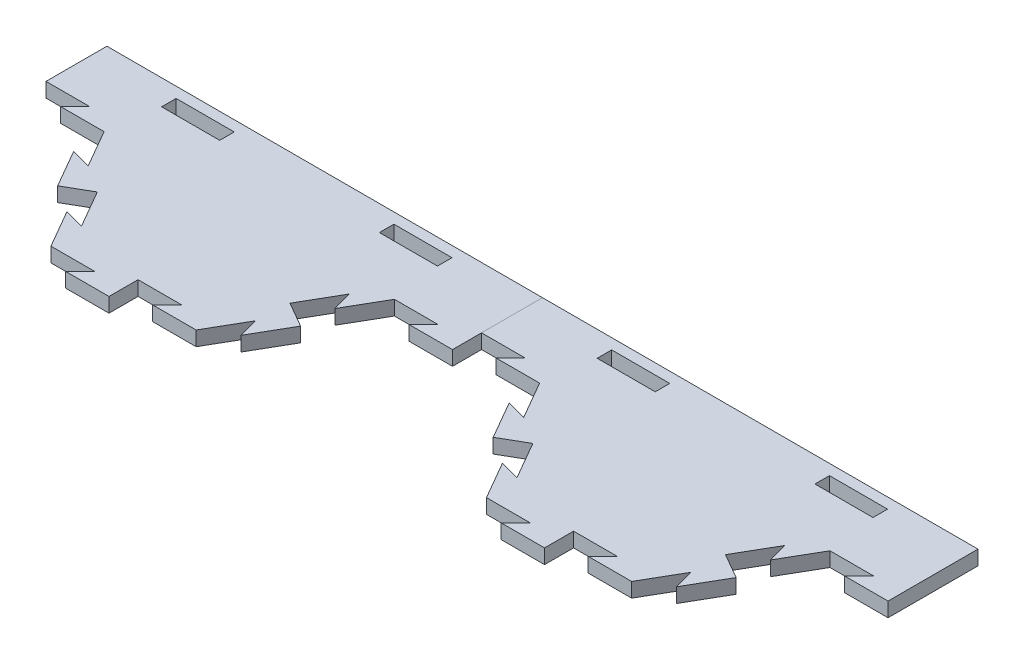
SolidWorks part; units mm, degrees
material "Cedar"
ref_plane "Front Plane" through (0, 0, 0) normal (0, 0, 1) x (1, 0, 0)
ref_plane "Top Plane" through (0, 0, 0) normal (0, 1, 0) x (1, 0, 0)
ref_plane "Right Plane" through (0, 0, 0) normal (1, 0, 0) x (0, 0, -1)
sketch "Sketch1" plane through (0, 0, 0) normal (0, 1, 0) x (1, 0, 0)
  line L0 (0, 0) -> (63.5, 0) construction
  line L1 (63.5, 0) -> (31.75, 54.9926)
  line L2 (31.75, 54.9926) -> (-31.75, 54.9926)
  line L3 (-31.75, 54.9926) -> (-63.5, 0)
  line L4 (-63.5, 0) -> (-31.75, -54.9926)
  line L5 (-31.75, -54.9926) -> (31.75, -54.9926)
  line L6 (31.75, -54.9926) -> (63.5, 0)
  circle A0 centre (0, 0) radius 54.9926 construction
  dimension "D1" = 63.5
extrude "Boss-Extrude1" add sketch "Sketch1" against normal blind 6.35
sketch "Sketch2" plane through (0, 0, 0) normal (0, 1, 0) x (1, 0, 0)
  point P1 (0, 0)
ref_axis "Axis1" through (0, 0, 0) along (0, 1, 0)
sketch "Sketch10" plane through (0, 0, 0) normal (0, 1, 0) x (1, 0, 0)
  line L0 (31.75, 54.9926) -> (41.275, 38.4948) construction
  line L1 (41.275, 38.4948) -> (32.6007, 40.8191)
  line L2 (32.6007, 40.8191) -> (42.1257, 24.3213)
  line L3 (42.1257, 24.3213) -> (47.625, 27.4963)
  line L4 (41.275, 38.4948) -> (47.625, 27.4963)
  line L5 (63.5, 0) -> (31.75, 54.9926) construction
  dimension "D1" = 45
  dimension "D2" = 6.35
extrude "Cut-Extrude4" cut sketch "Sketch10" against normal through all
sketch "Sketch11" plane through (0, 0, 0) normal (0, 1, 0) x (1, 0, 0)
  line L0 (47.625, 27.4963) -> (63.5, 0) construction
  line L1 (47.625, 27.4963) -> (53.1243, 30.6713)
  line L2 (53.1243, 30.6713) -> (62.6493, 14.1735)
  line L3 (62.6493, 14.1735) -> (53.975, 16.4978)
  line L4 (53.975, 16.4978) -> (47.625, 27.4963)
  line L5 (53.975, 16.4978) -> (63.5, 0) construction
  line L6 (53.975, 16.4978) -> (63.5, 0) construction
  line L7 (63.5, 0) -> (47.625, 27.4963) construction
  line L8 (31.75, -54.9926) -> (63.5, 0) construction
  dimension "D1" = 45
  dimension "D2" = 6.35
extrude "Boss-Extrude4" add sketch "Sketch11" against normal blind 6.35
pattern_circular "CirPattern7" count 6 over 360 about axis through (0, 0, 0) along (0, 1, 0) of "Cut-Extrude4", "Boss-Extrude4"
sketch "Sketch12" plane through (0, 0, 0) normal (0, 1, 0) x (1, 0, 0)
  line L0 (-63.5, 0) -> (63.5, 0)
  line L1 (63.5, 0) -> (63.5, 61.3426)
  line L2 (63.5, 61.3426) -> (-63.5, 61.3426)
  line L3 (-63.5, 61.3426) -> (-63.5, 0)
extrude "Cut-Extrude5" cut sketch "Sketch12" against normal through all
sketch "Sketch13" plane through (0, 0, 0) normal (0, 0, -1) x (-1, 0, 0)
  line L0 (0, -6.35) -> (0, 0) construction
  line L1 (95.25, -6.35) -> (-95.25, -6.35)
  line L2 (95.25, -6.35) -> (95.25, 0)
  line L3 (95.25, 0) -> (-95.25, 0)
  line L4 (-95.25, -6.35) -> (-95.25, 0)
  line L5 (63.5, -6.35) -> (-63.5, -6.35) construction
  dimension "D1" = 190.5
extrude "Boss-Extrude5" add sketch "Sketch13" along normal blind 32.9956
sketch "Sketch15" plane through (0, 0, 0) normal (0, 1, 0) x (1, 0, 0)
  line L0 (-63.5, 0) -> (-82.55, 0) construction
  line L1 (-82.55, 0) -> (-76.2, 6.35)
  line L2 (-76.2, 6.35) -> (-95.25, 6.35)
  line L3 (-95.25, 6.35) -> (-95.25, 0)
  line L4 (-82.55, 0) -> (-95.25, 0)
  line L6 (-95.25, 0) -> (-63.5, 0) construction
  line L7 (-95.25, 32.9956) -> (-95.25, 0) construction
  dimension "D1" = 45
  dimension "D2" = 6.35
extrude "Cut-Extrude6" cut sketch "Sketch15" against normal through all
sketch "Sketch16" plane through (0, 0, 0) normal (0, 1, 0) x (1, 0, 0)
  line L0 (63.5, 0) -> (82.55, 0) construction
  line L1 (82.55, 0) -> (76.2, -6.35)
  line L2 (76.2, -6.35) -> (95.25, -6.35)
  line L3 (95.25, -6.35) -> (95.25, 0)
  line L4 (82.55, 0) -> (95.25, 0)
  dimension "D1" = 45
  dimension "D2" = 6.35
extrude "Boss-Extrude6" add sketch "Sketch16" against normal up to surface (6.35 mm away) up to face at (-5.6696, -6.35, 24.6859)
sketch "Sketch17" plane through (0, 0, 0) normal (0, 1, 0) x (1, 0, 0)
  line L0 (0, 32.9956) -> (0, 17.3485) construction
  line L1 (-47.625, 25.172) -> (47.625, 25.172) construction
  line L2 (-60.325, 28.347) -> (-34.925, 28.347)
  line L3 (-60.325, 28.347) -> (-60.325, 21.997)
  line L4 (-60.325, 21.997) -> (-34.925, 21.997)
  line L5 (-34.925, 28.347) -> (-34.925, 21.997)
  line L6 (-60.325, 28.347) -> (-34.925, 21.997) construction
  line L7 (-60.325, 21.997) -> (-34.925, 28.347) construction
  line L8 (34.925, 28.347) -> (60.325, 28.347)
  line L9 (34.925, 28.347) -> (34.925, 21.997)
  line L10 (34.925, 21.997) -> (60.325, 21.997)
  line L11 (60.325, 28.347) -> (60.325, 21.997)
  line L12 (34.925, 28.347) -> (60.325, 21.997) construction
  line L13 (34.925, 21.997) -> (60.325, 28.347) construction
  line L14 (-95.25, 32.9956) -> (95.25, 32.9956) construction
  line L15 (-95.25, 17.3485) -> (95.25, 17.3485) construction
  line L16 (-95.25, 32.9956) -> (-95.25, 6.35) construction
  line L17 (95.25, 32.9956) -> (95.25, -6.35) construction
  point P4 (0, 25.172)
  point P5 (0, 25.172)
  point P14 (-95.25, 21.1303)
  dimension "D1" = 6.35
  dimension "D2" = 25.4
  dimension "D3" = 6.35
  dimension "D4" = 25.4
  dimension "D5" = 95.25
  dimension "D6" = 15.6471
extrude "Cut-Extrude8" cut sketch "Sketch17" against normal through all
pattern_linear "LPattern1" count 2 spacing 190.5 along (1, 0, 0) of bodies 135
